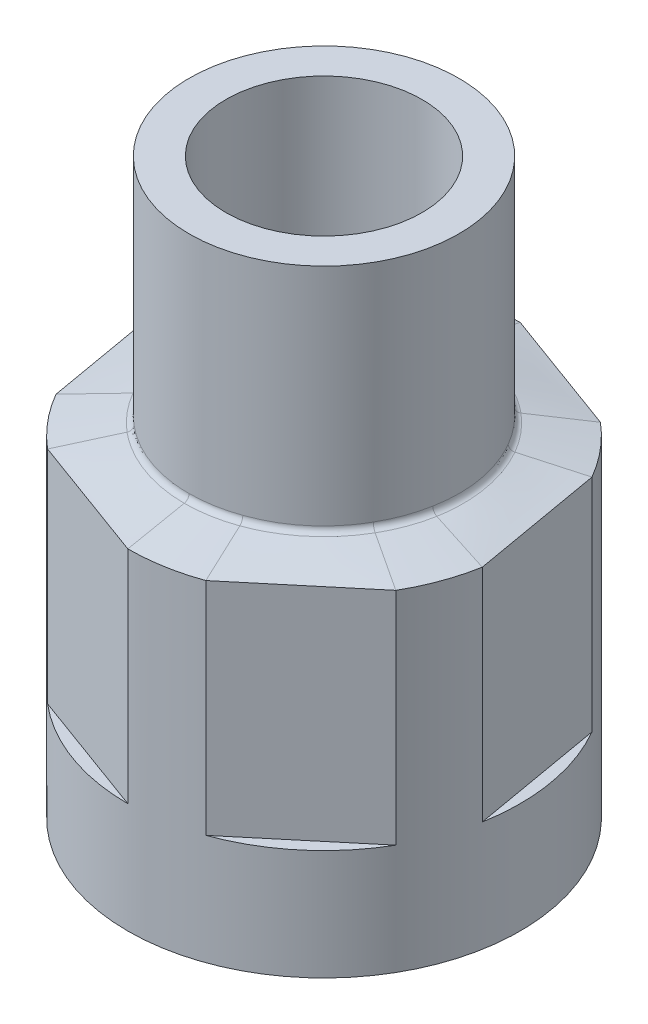
SolidWorks part; units mm, degrees
ref_plane "Спереди" through (0, 0, 0) normal (0, 0, 1) x (1, 0, 0)
ref_plane "Сверху" through (0, 0, 0) normal (0, 1, 0) x (1, 0, 0)
ref_plane "Справа" through (0, 0, 0) normal (1, 0, 0) x (0, 0, -1)
sketch "Эскиз1" plane through (0, 0, 0) normal (0, 1, 0) x (1, 0, 0)
  circle A0 centre (0, 0) radius 11
  dimension "D1" = 22
ref_plane "Плоскость1" through (0, -18.75, 0) normal (0, 1, 0) x (1, 0, 0)
sketch "Эскиз2" plane through (0, -18.75, 0) normal (0, 1, 0) x (1, 0, 0)
  circle A2 centre (0, 0) radius 11
  dimension "D1" = 22
loft "По сечениям1" add profiles "Эскиз2", "Эскиз1" connector at (-7.995, -18.75, -7.5552) connector at (-8.0065, 0, -7.5429)
cosmetic thread "Условное изображение резьбы3" parameters "D2"=20.344
sketch "Эскиз3" plane through (0, 0, 0) normal (0, 1, 0) x (1, 0, 0)
  circle A0 centre (0, 0) radius 8
  circle A1 centre (0, 0) radius 11 construction
  dimension "D1" = 3
extrude "Вырез-Вытянуть1" cut sketch "Эскиз3" against normal blind 12
sketch "Эскиз4" plane through (0, -12, 0) normal (0, 1, 0) x (1, 0, 0)
  circle A0 centre (0, 0) radius 6.5
  circle A1 centre (0, 0) radius 8 construction
  dimension "D1" = 1.5
extrude "Вырез-Вытянуть2" cut sketch "Эскиз4" against normal through all
ref_plane "Плоскость2" through (0, -3.5, 0) normal (0, 1, 0) x (1, 0, 0)
ref_plane "Плоскость3" through (0, -19.75, 0) normal (0, 1, 0) x (1, 0, 0)
sketch "Эскиз6" plane through (0, -19.75, 0) normal (0, 1, 0) x (1, 0, 0)
  line L1 (-5.4169, 15.0551) -> (-13.8564, 8)
  line L2 (-15.7466, 2.8364) -> (-13.8564, -8)
  line L3 (-10.3297, -12.2187) -> (0, -16)
  line L4 (5.4169, -15.0551) -> (13.8564, -8)
  line L5 (15.7466, -2.8364) -> (13.8564, 8)
  line L6 (10.3297, 12.2188) -> (0, 16)
  arc A0 (-13.8564, 8) -> (-15.7466, 2.8364) centre (0, 0) ccw
  circle A1 centre (0, 0) radius 15.025 construction
  arc A2 (-13.8564, -8) -> (-10.3297, -12.2187) centre (0, 0) ccw
  arc A3 (0, 16) -> (-5.4169, 15.0551) centre (0, 0) ccw
  arc A4 (13.8564, 8) -> (10.3297, 12.2188) centre (0, 0) ccw
  arc A5 (13.8564, -8) -> (15.7466, -2.8364) centre (0, 0) ccw
  arc A6 (0, -16) -> (5.4169, -15.0551) centre (0, 0) ccw
  point P3 (-13.8564, 8)
  point P11 (-5.4169, 15.0551)
  dimension "D1" = 32
  dimension "D2" = 11
ref_plane "Плоскость4" through (0, -37.75, 0) normal (0, 1, 0) x (1, 0, 0)
sketch "Эскиз7" plane through (0, -37.75, 0) normal (0, 1, 0) x (1, 0, 0)
  line L0 (-10.3297, -12.2187) -> (0, -16) construction
  line L1 (5.4169, -15.0551) -> (13.8564, -8) construction
  line L2 (15.7466, -2.8364) -> (13.8564, 8) construction
  line L3 (10.3297, 12.2188) -> (0, 16) construction
  line L4 (-5.4169, 15.0551) -> (-13.8564, 8) construction
  line L5 (-15.7466, 2.8364) -> (-13.8564, -8) construction
  line L6 (-10.3297, -12.2187) -> (0, -16)
  line L7 (5.4169, -15.0551) -> (13.8564, -8)
  line L8 (15.7466, -2.8364) -> (13.8564, 8)
  line L9 (10.3297, 12.2188) -> (0, 16)
  line L10 (-5.4169, 15.0551) -> (-13.8564, 8)
  line L11 (-15.7466, 2.8364) -> (-13.8564, -8)
  arc A0 (0, -16) -> (5.4169, -15.0551) centre (0, 0) ccw construction
  arc A1 (13.8564, -8) -> (15.7466, -2.8364) centre (0, 0) ccw construction
  arc A2 (13.8564, 8) -> (10.3297, 12.2188) centre (0, 0) ccw construction
  arc A3 (0, 16) -> (-5.4169, 15.0551) centre (0, 0) ccw construction
  arc A4 (-13.8564, 8) -> (-15.7466, 2.8364) centre (0, 0) ccw construction
  arc A5 (-13.8564, -8) -> (-10.3297, -12.2187) centre (0, 0) ccw construction
  arc A6 (0, -16) -> (5.4169, -15.0551) centre (0, 0) ccw
  arc A7 (13.8564, -8) -> (15.7466, -2.8364) centre (0, 0) ccw
  arc A8 (13.8564, 8) -> (10.3297, 12.2188) centre (0, 0) ccw
  arc A9 (0, 16) -> (-5.4169, 15.0551) centre (0, 0) ccw
  arc A10 (-13.8564, 8) -> (-15.7466, 2.8364) centre (0, 0) ccw
  arc A11 (-13.8564, -8) -> (-10.3297, -12.2187) centre (0, 0) ccw
loft "По сечениям2" add profiles "Эскиз6", "Эскиз2<3>" connector at (15.7466, -19.75, 2.8364) connector at (-8.4845, -18.75, -7.001)
sketch "Эскиз2<3>" plane through (0, -18.75, 0) normal (0, 1, 0) x (1, 0, 0) same geometry as "Эскиз2"
loft "По сечениям3" add profiles "Эскиз7", "Эскиз6<3>"
sketch "Эскиз6<3>" plane through (0, -19.75, 0) normal (0, 1, 0) x (1, 0, 0) same geometry as "Эскиз6"
sketch "Эскиз8" plane through (0, -37.75, 0) normal (0, 1, 0) x (1, 0, 0)
  circle A0 centre (0, 0) radius 16
  dimension "D1" = 32
ref_plane "Плоскость5" through (0, -46.75, 0) normal (0, 1, 0) x (1, 0, 0)
sketch "Эскиз9" plane through (0, -46.75, 0) normal (0, 1, 0) x (1, 0, 0)
  circle A0 centre (0, 0) radius 16 construction
  circle A1 centre (0, 0) radius 16
extrude "Бобышка-Вытянуть1" add sketch "Эскиз8" against normal blind 9 contours A0
ref_plane "Плоскость6" through (0, -47.75, 0) normal (0, 1, 0) x (1, 0, 0)
sketch "Эскиз10" plane through (0, -47.75, 0) normal (0, 1, 0) x (1, 0, 0)
  circle A0 centre (0, 0) radius 13.9
  dimension "D1" = 27.8
extrude "Бобышка-Вытянуть2" add sketch "Эскиз10" along normal blind 1
sketch "Эскиз11" plane through (0, -47.75, 0) normal (0, -1, 0) x (1, 0, 0)
  circle A0 centre (0, 0) radius 10
  dimension "D1" = 20
extrude "Вырез-Вытянуть3" cut sketch "Эскиз11" against normal blind 20
cosmetic thread "Условное изображение резьбы4" parameters "D2"=22
sketch "Эскиз12" plane through (0, -27.75, 0) normal (0, -1, 0) x (1, 0, 0)
  circle A0 centre (0, 0) radius 7
  circle A1 centre (0, 0) radius 10 construction
  dimension "D1" = 3
ref_plane "Плоскость7" through (0, -18.75, 0) normal (0, 1, 0) x (1, 0, 0)
extrude "Вырез-Вытянуть4" cut sketch "Эскиз12" against normal up to surface (9 mm away) up to plane "Плоскость7"
fillet "Скругление1" radius 0.5 12 edges
